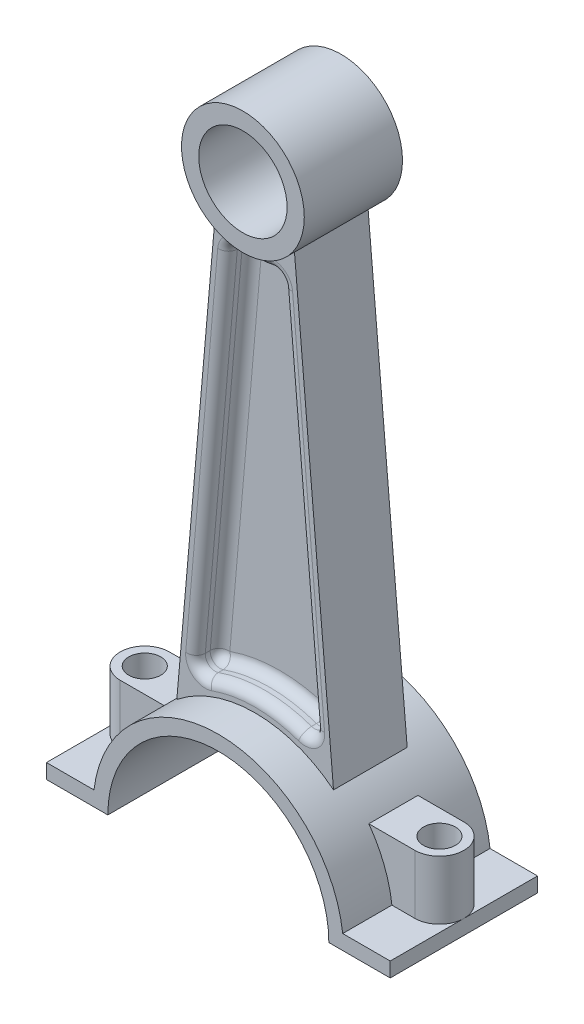
SolidWorks part; units mm, degrees
ref_plane "Front Plane" through (0, 0, 0) normal (0, 0, 1) x (1, 0, 0)
ref_plane "Top Plane" through (0, 0, 0) normal (0, 1, 0) x (1, 0, 0)
ref_plane "Right Plane" through (0, 0, 0) normal (1, 0, 0) x (0, 0, -1)
sketch "Sketch2" plane through (0, 0, 0) normal (0, 0, 1) x (1, 0, 0)
  line L0 (0, 0) -> (0, -120.4) construction
  line L1 (-35, -120.4) -> (-22.5, -120.4)
  line L2 (22.5, -120.4) -> (35, -120.4)
  line L3 (25.3229, -117.4) -> (35, -117.4)
  line L4 (-35, -117.4) -> (-25.3229, -117.4)
  line L5 (35, -120.4) -> (35, -117.4)
  line L6 (-35, -120.4) -> (-35, -117.4)
  line L7 (-8, -9.6047) -> (-15.9529, -100.5064)
  line L8 (8, -9.6047) -> (15.9529, -100.5064)
  circle A0 centre (0, 0) radius 9
  circle A1 centre (0, 0) radius 12.5
  arc A2 (22.5, -120.4) -> (-22.5, -120.4) centre (0, -120.4) ccw
  arc A3 (25.3229, -117.4) -> (-25.3229, -117.4) centre (0, -120.4) ccw
  dimension "D1" = 25
  dimension "D2" = 18
  dimension "D4" = 45
  dimension "D3" = 120.4
  dimension "D5" = 70
  dimension "D7" = 8
  dimension "D8" = 5
  dimension "D6" = 3
extrude "Boss-Extrude1" add sketch "Sketch2" along normal mid plane 20 contours A0 A1 region at (-5.1533, 10.9991, 0)
extrude "Boss-Extrude2" add sketch "Sketch2<3>" along normal mid plane 30 separate body contours A3 L0 A2 L2 L5 L3 | L0 A3 L4 L6 L1 A2 region at (8.3111, -96.7509, 0) region at (-0.433, -96.4, 0)
sketch "Sketch2<3>" plane through (0, 0, 0) normal (0, 0, 1) x (1, 0, 0) same geometry as "Sketch2"
extrude "Boss-Extrude3" add sketch "Sketch2<4>" along normal mid plane 15 contours L0 A1 L7 A3 | A1 L0 A3 L8 region at (6.2653, -58.5545, 0) region at (-6.2653, -58.5545, 0)
sketch "Sketch2<4>" plane through (0, 0, 0) normal (0, 0, 1) x (1, 0, 0) same geometry as "Sketch2"
sketch "Sketch3" plane through (0, 0, 0) normal (0, 0, 1) x (1, 0, 0)
  line L4 (-5.4187, -14.522) -> (-12.4385, -94.7576)
  line L5 (12.4385, -94.7576) -> (5.4187, -14.522)
  line L6 (-5.4187, -14.522) -> (-12.4385, -94.7576)
  line L7 (12.4385, -94.7576) -> (5.4187, -14.522)
  arc A4 (12.4385, -94.7576) -> (-12.4385, -94.7576) centre (0, -120.4) ccw
  arc A5 (-5.4187, -14.522) -> (5.4187, -14.522) centre (0, 0) ccw
  arc A6 (12.4385, -94.7576) -> (-12.4385, -94.7576) centre (0, -120.4) ccw
  arc A7 (-5.4187, -14.522) -> (5.4187, -14.522) centre (0, 0) ccw
  dimension "D1" = 3
extrude "Cut-Extrude2" cut sketch "Sketch3" against normal blind 5 from offset 7.5
mirror "Mirror1" about plane through (0, 0, 0) normal (0, 0, 1) of "Cut-Extrude2"
sketch "Sketch4" plane through (0, -117.4, 0) normal (0, 1, 0) x (1, 0, 0)
  line L0 (35, -15) -> (35, 15) construction
  line L1 (18, 5.0196) -> (30, 5.0196)
  line L2 (18, 5.0196) -> (18, -4.9804)
  line L3 (18, -4.9804) -> (30, -4.9804)
  arc A0 (30, -4.9804) -> (30, 5.0196) centre (30, 0.0196) ccw
  circle A1 centre (30, 0.0196) radius 3.25
  point P0 (23.9187, 0)
  line M4 (25.3229, 15) -> (25.3229, -15)
  dimension "D1" = 10
  dimension "D3" = 6.5
  dimension "D2" = 12
extrude "Boss-Extrude8" add sketch "Sketch4" against normal up to body from offset 12 separate body contours L3 A0 L1 A1 M4 | A1 | L1 A0 L3 L2 region at (27.6615, -117.4, -4.8804) region at (30, -117.4, -0.0196)
extrude "Cut-Extrude3" cut sketch "Sketch4<14>" along normal through all both and the other way through all contours A1
sketch "Sketch4<14>" plane through (0, -117.4, 0) normal (0, 1, 0) x (1, 0, 0) same geometry as "Sketch4"
mirror "Mirror2" about plane through (0, 0, 0) normal (1, 0, 0) of "Cut-Extrude3", "Boss-Extrude8"
fillet "Fillet1" radius 2 12 edges at (12.4385, -94.7576, -5) (-12.4385, -94.7576, -5) (0, -91.9, -7.5) (0, -91.9, -2.5) (8.9286, -54.6398, -7.5) (8.9286, -54.6398, -2.5) (5.4187, -14.522, -5) (-5.4187, -14.522, -5) (-8.9286, -54.6398, -2.5) (0, -15.5, -2.5) (-8.9286, -54.6398, -7.5) (0, -15.5, -7.5)
fillet "Fillet5" radius 2 12 edges at (-5.4187, -14.522, 5) (5.4187, -14.522, 5) (12.4385, -94.7576, 5) (-12.4385, -94.7576, 5) (0, -91.9, 2.5) (0, -91.9, 7.5) (8.9286, -54.6398, 2.5) (8.9286, -54.6398, 7.5) (0, -15.5, 7.5) (-8.9286, -54.6398, 2.5) (-8.9286, -54.6398, 7.5) (0, -15.5, 2.5)
